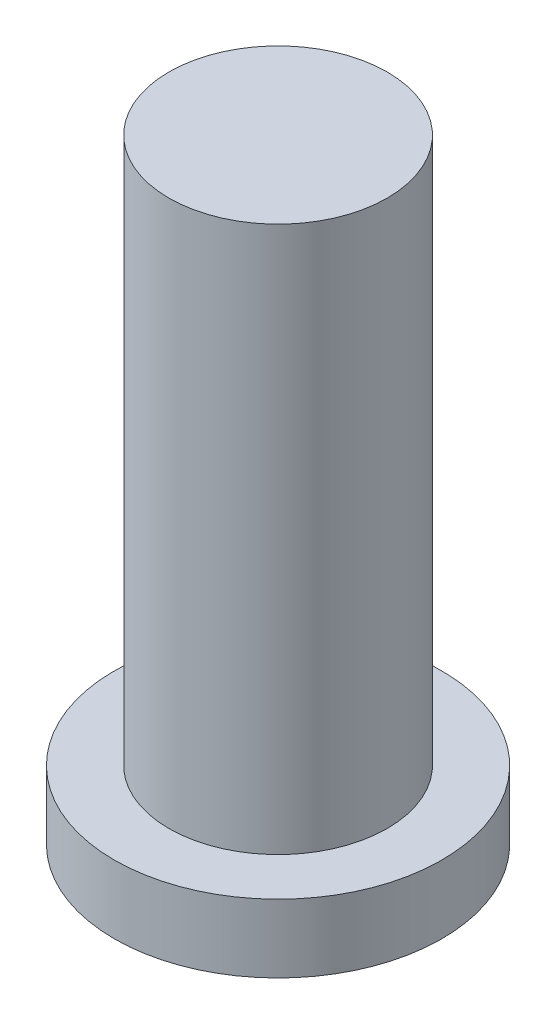
SolidWorks part; units mm, degrees
ref_plane "Front Plane" through (0, 0, 0) normal (0, 0, 1) x (1, 0, 0)
ref_plane "Top Plane" through (0, 0, 0) normal (0, 1, 0) x (1, 0, 0)
ref_plane "Right Plane" through (0, 0, 0) normal (1, 0, 0) x (0, 0, -1)
sketch "Sketch1" plane through (0, 0, 0) normal (0, 1, 0) x (1, 0, 0)
  circle A0 centre (0, 0) radius 2.4
  circle A1 centre (0, 0) radius 1.6
  dimension "D1" = 3.2
  dimension "D2" = 4.8
extrude "Boss-Extrude1" add sketch "Sketch1" along normal blind 1 contours A1 | A0 A1 | A1 | A0 region at (-2.3321, 0, 0) region at (0, 0, 0)
extrude "Boss-Extrude2" add sketch "Sketch1<4>" along normal blind 8 from surface contours A1 starting at face at (0, 1, 2.4)
sketch "Sketch1<4>" plane through (0, 0, 0) normal (0, 1, 0) x (1, 0, 0) same geometry as "Sketch1"
